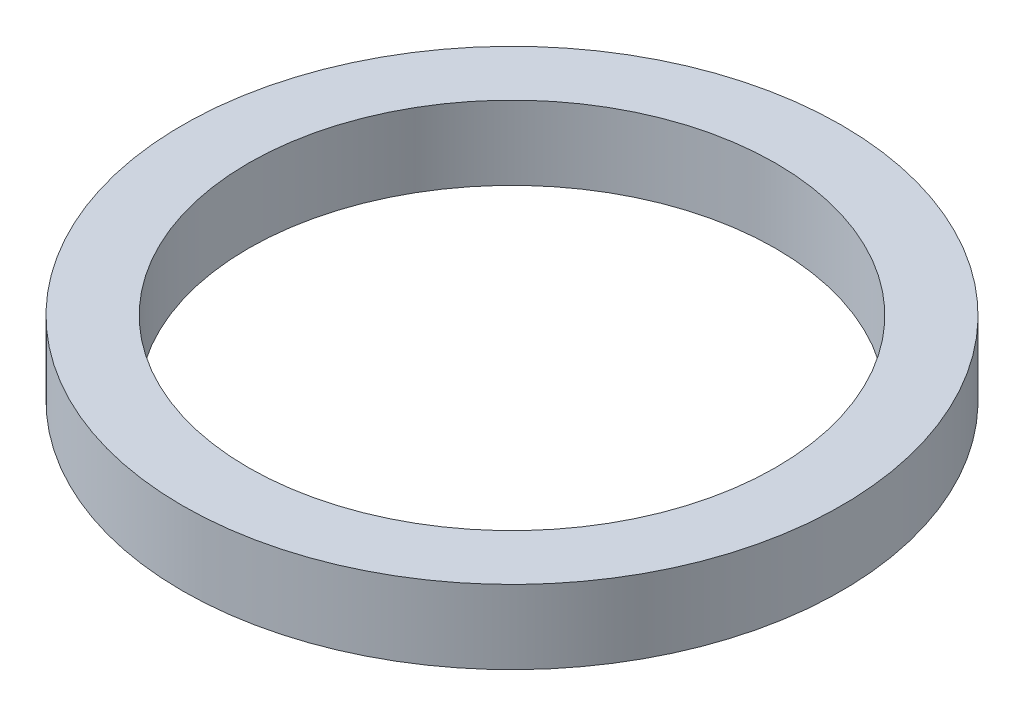
SolidWorks part; units mm, degrees
ref_plane "Front Plane" through (0, 0, 0) normal (0, 0, 1) x (1, 0, 0)
ref_plane "Top Plane" through (0, 0, 0) normal (0, 1, 0) x (1, 0, 0)
ref_plane "Right Plane" through (0, 0, 0) normal (1, 0, 0) x (0, 0, -1)
sketch "Sketch1" plane through (0, 0, 0) normal (0, 1, 0) x (1, 0, 0)
  circle A0 centre (0, 0) radius 62.5
  dimension "FLANGE_OD" = 125
extrude "Boss-Extrude1" add sketch "Sketch1" along normal blind 14
sketch "Sketch2" plane through (0, 0, 0) normal (0, 1, 0) x (1, 0, 0)
  circle A0 centre (0, 0) radius 50
  dimension "BORE_D" = 100
extrude "Cut-Extrude1" cut sketch "Sketch2" along normal through all
sketch "Sketch3" plane through (0, 14, 0) normal (0, 1, 0) x (1, 0, 0)
  circle A0 centre (0, 0) radius 28.538 construction
  circle A1 centre (-28.538, 0) radius 1.6681
  dimension "BOLT_D" = 3.3363
  dimension "BOLT_PCD" = 57.0761
extrude "Cut-Extrude2" cut sketch "Sketch3" against normal blind 8.5499 rebuild error yes
pattern_circular "CirPattern1" count 6 over 360 rebuild error yes
